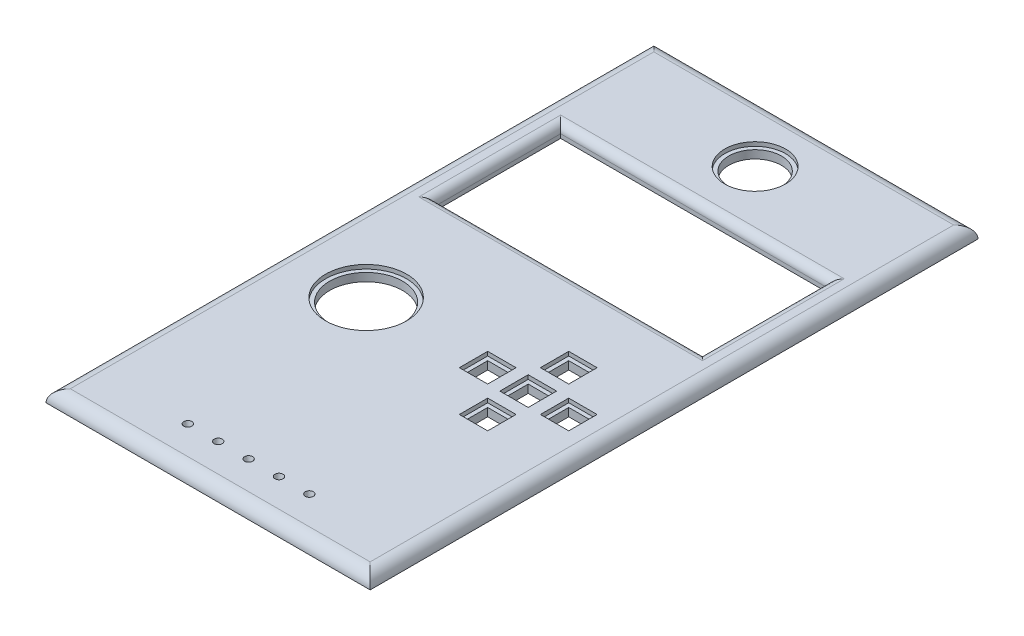
SolidWorks part; units mm, degrees
ref_plane "Front Plane" through (0, 0, 0) normal (0, 0, 1) x (1, 0, 0)
ref_plane "Top Plane" through (0, 0, 0) normal (0, 1, 0) x (1, 0, 0)
ref_plane "Right Plane" through (0, 0, 0) normal (1, 0, 0) x (0, 0, -1)
sketch "Sketch1" plane through (0, 0, 0) normal (0, 1, 0) x (1, 0, 0)
  line L1 (-40, 75) -> (40, 75)
  line L2 (-40, 75) -> (-40, -75)
  line L3 (-40, -75) -> (40, -75)
  line L4 (40, 75) -> (40, -75)
  line L5 (-40, 75) -> (40, -75) construction
  line L6 (-40, -75) -> (40, 75) construction
  point P0 (0, 0)
  dimension "D1" = 150
  dimension "D2" = 80
extrude "Boss-Extrude1" add sketch "Sketch1" along normal blind 3
sketch "Sketch2" plane through (0, 3, 0) normal (0, 1, 0) x (1, 0, 0)
  line L0 (0, 75) -> (0, -75) construction
  line L1 (40, 75) -> (-40, 75) construction
  line L2 (-40, -75) -> (40, -75) construction
  line L4 (-33, 45) -> (33, 45)
  line L5 (-33, 45) -> (-33, 14)
  line L6 (-33, 14) -> (33, 14)
  line L7 (33, 45) -> (33, 14)
  line L8 (-33, 45) -> (33, 14) construction
  line L9 (-33, 14) -> (33, 45) construction
  point P6 (0, 29.5)
  dimension "D1" = 30
  dimension "D2" = 31
  dimension "D3" = 66
extrude "Cut-Extrude1" cut sketch "Sketch2" against normal blind 3
sketch "Sketch4" plane through (0, 3, 0) normal (0, 1, 0) x (1, 0, 0)
  line L0 (40, 75) -> (-40, 75) construction
  line L1 (40, -75) -> (40, 75) construction
  circle A0 centre (0, 60) radius 7.5
  point P4 (0, 75)
  dimension "D3" = 15
  dimension "D1" = 15
  dimension "D2" = 40
extrude "Cut-Extrude2" cut sketch "Sketch4" against normal blind 1
sketch "Sketch5" plane through (0, 2, 0) normal (0, 1, 0) x (1, 0, 0)
  circle A0 centre (0, 60) radius 6.5
  dimension "D1" = 13
extrude "Cut-Extrude3" cut sketch "Sketch5" against normal blind 19
sketch "Sketch6" plane through (0, 3, 0) normal (0, 1, 0) x (1, 0, 0)
  line L0 (-40, 75) -> (-40, -75) construction
  line L1 (-33, 14) -> (33, 14) construction
  circle A0 centre (-20, -16) radius 10
  dimension "D3" = 20
  dimension "D1" = 20
  dimension "D2" = 30
extrude "Cut-Extrude4" cut sketch "Sketch6" against normal blind 1
sketch "Sketch8" plane through (0, 2, 0) normal (0, 1, 0) x (1, 0, 0)
  circle A0 centre (-20, -16) radius 9
  dimension "D1" = 18
extrude "Cut-Extrude5" cut sketch "Sketch8" against normal through all
sketch "Sketch9" plane through (0, 3, 0) normal (0, 1, 0) x (1, 0, 0)
  line L0 (0, 14) -> (0, -75) construction
  line L1 (-33, 14) -> (33, 14) construction
  line L2 (-40, -75) -> (40, -75) construction
  line L3 (-20, -16) -> (40, -16) construction
  line L4 (40, -75) -> (40, 75) construction
  line L5 (20, 14) -> (20, -76.3729) construction
  line L6 (65.757, -6) -> (-16.903, -6) construction
  line L7 (-10.5129, -26) -> (67.6122, -26) construction
  line L8 (10, 14) -> (10, -75) construction
  line L9 (16.5, -2.5) -> (23.5, -2.5)
  line L10 (16.5, -2.5) -> (16.5, -9.5)
  line L11 (16.5, -9.5) -> (23.5, -9.5)
  line L12 (23.5, -2.5) -> (23.5, -9.5)
  line L13 (16.5, -2.5) -> (23.5, -9.5) construction
  line L14 (16.5, -9.5) -> (23.5, -2.5) construction
  line L15 (16.5, -22.5) -> (23.5, -22.5)
  line L16 (16.5, -22.5) -> (16.5, -29.5)
  line L17 (16.5, -29.5) -> (23.5, -29.5)
  line L18 (23.5, -22.5) -> (23.5, -29.5)
  line L19 (16.5, -22.5) -> (23.5, -29.5) construction
  line L20 (16.5, -29.5) -> (23.5, -22.5) construction
  line L21 (30, 14) -> (30, -77.8158) construction
  line L23 (6.5, -12.5) -> (13.5, -12.5)
  line L24 (6.5, -12.5) -> (6.5, -19.5)
  line L25 (6.5, -19.5) -> (13.5, -19.5)
  line L26 (13.5, -12.5) -> (13.5, -19.5)
  line L27 (6.5, -12.5) -> (13.5, -19.5) construction
  line L28 (6.5, -19.5) -> (13.5, -12.5) construction
  line L29 (26.5, -12.5) -> (33.5, -12.5)
  line L30 (26.5, -12.5) -> (26.5, -19.5)
  line L31 (26.5, -19.5) -> (33.5, -19.5)
  line L32 (33.5, -12.5) -> (33.5, -19.5)
  line L33 (26.5, -12.5) -> (33.5, -19.5) construction
  line L34 (26.5, -19.5) -> (33.5, -12.5) construction
  point P17 (20, -6)
  point P22 (20, -26)
  point P31 (10, -16)
  point P36 (30, -16)
  dimension "D1" = 20
  dimension "D2" = 10
  dimension "D3" = 10
  dimension "D4" = 10
  dimension "D5" = 10
  dimension "D6" = 7
  dimension "D7" = 7
  dimension "D8" = 7
  dimension "D9" = 7
  dimension "D10" = 7
  dimension "D11" = 7
  dimension "D12" = 7
  dimension "D13" = 7
extrude "Cut-Extrude6" cut sketch "Sketch9" against normal blind 1
sketch "Sketch12" plane through (0, 2, 0) normal (0, 1, 0) x (1, 0, 0)
  line L0 (16.5, -2.5) -> (23.5, -9.5) construction
  line L1 (17.5, -3.5) -> (22.5, -3.5)
  line L2 (17.5, -3.5) -> (17.5, -8.5)
  line L3 (17.5, -8.5) -> (22.5, -8.5)
  line L4 (22.5, -3.5) -> (22.5, -8.5)
  line L5 (17.5, -3.5) -> (22.5, -8.5) construction
  line L6 (17.5, -8.5) -> (22.5, -3.5) construction
  line L7 (6.5, -12.5) -> (13.5, -19.5) construction
  line L8 (7.5, -13.5) -> (12.5, -13.5)
  line L9 (7.5, -13.5) -> (7.5, -18.5)
  line L10 (7.5, -18.5) -> (12.5, -18.5)
  line L11 (12.5, -13.5) -> (12.5, -18.5)
  line L12 (7.5, -13.5) -> (12.5, -18.5) construction
  line L13 (7.5, -18.5) -> (12.5, -13.5) construction
  line L14 (26.5, -12.5) -> (33.5, -19.5) construction
  line L15 (27.5, -13.5) -> (32.5, -13.5)
  line L16 (27.5, -13.5) -> (27.5, -18.5)
  line L17 (27.5, -18.5) -> (32.5, -18.5)
  line L18 (32.5, -13.5) -> (32.5, -18.5)
  line L19 (27.5, -13.5) -> (32.5, -18.5) construction
  line L20 (27.5, -18.5) -> (32.5, -13.5) construction
  line L21 (16.5, -22.5) -> (23.5, -29.5) construction
  line L22 (17.5, -23.5) -> (22.5, -23.5)
  line L23 (17.5, -23.5) -> (17.5, -28.5)
  line L24 (17.5, -28.5) -> (22.5, -28.5)
  line L25 (22.5, -23.5) -> (22.5, -28.5)
  line L26 (17.5, -23.5) -> (22.5, -28.5) construction
  line L27 (17.5, -28.5) -> (22.5, -23.5) construction
  point P0 (20, -6)
  point P8 (10, -16)
  point P16 (30, -16)
  point P24 (20, -26)
  dimension "D1" = 5
  dimension "D2" = 5
  dimension "D3" = 5
  dimension "D4" = 5
extrude "Cut-Extrude7" cut sketch "Sketch12" against normal through all
sketch "Sketch14" plane through (0, 3, 0) normal (0, 1, 0) x (1, 0, 0)
  line L0 (0, 0) -> (0, -78.0794) construction
  line L1 (-40, -65) -> (40, -65) construction
  line L2 (-40, 75) -> (-40, -75) construction
  line L3 (40, -75) -> (40, 75) construction
  line L4 (-40, -75) -> (40, -75) construction
  circle A0 centre (0, -65) radius 1
  circle A1 centre (-7.5, -65) radius 1
  circle A2 centre (-15, -65) radius 1
  circle A3 centre (7.5, -65) radius 1
  circle A4 centre (15, -65) radius 1
  dimension "D2" = 2
  dimension "D1" = 10
  dimension "D3" = 7.5
  dimension "D4" = 7.5
extrude "Cut-Extrude8" cut sketch "Sketch14" against normal through all draft 15
fillet "Fillet1" radius 3 4 edges at (40, 3, 0) (0, 3, -75) (-40, 3, 0) (0, 3, 75)
fillet "Fillet2" radius 2 4 edges at (33, 3, -29.5) (0, 3, -45) (-33, 3, -29.5) (0, 3, -14)
sketch "Sketch15" plane through (0, 3, 0) normal (0, 1, 0) x (1, 0, 0)
  line L0 (20, -9.5) -> (20, -22.5) construction
  line L1 (16.5, -9.5) -> (23.5, -9.5) construction
  line L2 (23.5, -22.5) -> (16.5, -22.5) construction
  line L3 (13.5, -16) -> (26.5, -16) construction
  line L4 (13.5, -19.5) -> (13.5, -12.5) construction
  line L5 (26.5, -12.5) -> (26.5, -19.5) construction
  line L7 (16.5, -12.5) -> (23.5, -12.5)
  line L8 (16.5, -12.5) -> (16.5, -19.5)
  line L9 (16.5, -19.5) -> (23.5, -19.5)
  line L10 (23.5, -12.5) -> (23.5, -19.5)
  line L11 (16.5, -12.5) -> (23.5, -19.5) construction
  line L12 (16.5, -19.5) -> (23.5, -12.5) construction
  point P12 (20, -16)
  dimension "D1" = 7
  dimension "D2" = 7
extrude "Cut-Extrude9" cut sketch "Sketch15" against normal blind 1
sketch "Sketch16" plane through (0, 2, 0) normal (0, 1, 0) x (1, 0, 0)
  line L0 (16.5, -16) -> (23.5, -16) construction
  line L1 (16.5, -12.5) -> (16.5, -19.5) construction
  line L2 (23.5, -19.5) -> (23.5, -12.5) construction
  line L4 (17.5, -13.5) -> (22.5, -13.5)
  line L5 (17.5, -13.5) -> (17.5, -18.5)
  line L6 (17.5, -18.5) -> (22.5, -18.5)
  line L7 (22.5, -13.5) -> (22.5, -18.5)
  line L8 (17.5, -13.5) -> (22.5, -18.5) construction
  line L9 (17.5, -18.5) -> (22.5, -13.5) construction
  point P6 (20, -16)
  dimension "D1" = 5
  dimension "D2" = 5
extrude "Cut-Extrude10" cut sketch "Sketch16" against normal through all
